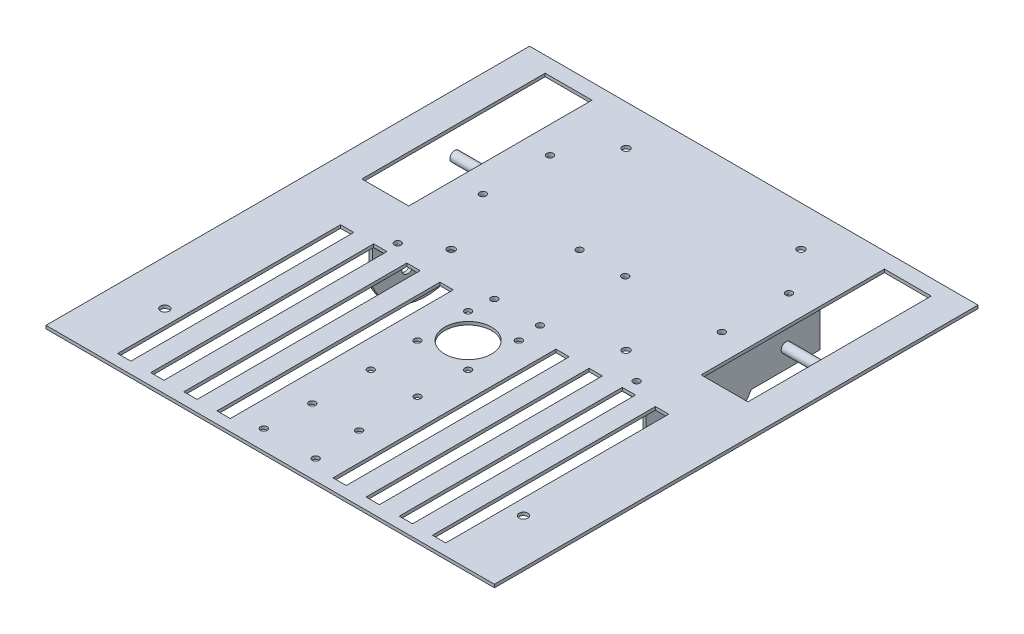
SolidWorks part; units mm, degrees
ref_plane "Front Plane" through (0, 0, 0) normal (0, 0, 1) x (1, 0, 0)
ref_plane "Top Plane" through (0, 0, 0) normal (0, 1, 0) x (1, 0, 0)
ref_plane "Right Plane" through (0, 0, 0) normal (1, 0, 0) x (0, 0, -1)
sketch "Sketch2" plane through (0, 0, 0) normal (0, 1, 0) x (1, 0, 0)
  line L7 (-172.2662, -88.2141) -> (57.7338, -88.2141)
  line L8 (17.7338, 151.7859) -> (41.7338, 151.7859)
  line L45 (17.7338, 151.7859) -> (17.7338, 57.7859)
  line L46 (17.7338, 57.7859) -> (41.7338, 57.7859)
  line L47 (41.7338, 151.7859) -> (41.7338, 57.7859)
  line L48 (-156.2662, 151.7859) -> (-132.2662, 151.7859)
  line L49 (-156.2662, 151.7859) -> (-156.2662, 57.7859)
  line L50 (-156.2662, 57.7859) -> (-132.2662, 57.7859)
  line L51 (-132.2662, 151.7859) -> (-132.2662, 57.7859)
  line L72 (57.7338, 159.7859) -> (-172.2662, 159.7859)
  line L74 (57.7338, -88.2141) -> (57.7338, 159.7859)
  line L79 (-172.2662, -88.2141) -> (-172.2662, 159.7859)
  dimension "D2" = 16
  dimension "D3" = 16
  dimension "D6" = 230
  dimension "D8" = 24
  dimension "D9" = 24
  dimension "D12" = 8
  dimension "D13" = 94
extrude "Boss-Extrude1" add sketch "Sketch2" along normal blind 1.6
ref_plane "Plane3" through (-57.2662, 0, 0) normal (1, 0, 0) x (0, 0, -1)
sketch "Sketch4" plane through (0, 0, 0) normal (0, -1, 0) x (1, 0, 0)
  line L0 (-128.2662, -122.8126) -> (-128.2662, -33.5103)
  line L1 (-128.2662, -122.8126) -> (-110.4256, -122.8126)
  line L2 (-128.2662, -33.5103) -> (-110.4287, -33.5103)
  line L5 (-64.765, -32.9867) -> (-64.765, -87.1773)
  line L6 (-64.765, -32.9867) -> (-73.1795, -32.9867)
  line L7 (-64.765, -87.1773) -> (-73.1795, -87.1773)
  line L9 (-110.4287, -33.5103) -> (-110.4287, -55.4044)
  line L10 (-110.4287, -55.4044) -> (-73.1795, -55.4044)
  line L11 (-73.1795, -55.4044) -> (-73.1795, -32.9867)
  line L12 (-73.1795, -87.1773) -> (-73.1795, -65.4044)
  line L13 (-73.1795, -65.4044) -> (-110.4256, -65.4044)
  line L14 (-110.4256, -65.4044) -> (-110.4256, -122.8126)
extrude "Boss-Extrude3" add sketch "Sketch4" along normal blind 1.6129 separate body
sketch "Sketch6" plane through (-128.2662, 113.8349, 0) normal (1, 0, 0) x (0, -1, 0)
  line L0 (115.4478, 33.5103) -> (113.8349, 33.5103)
  line L1 (113.8349, 33.5103) -> (113.8349, 122.8126)
  line L4 (132.89, 33.5103) -> (115.4478, 33.5103)
  line L7 (135.5889, 122.8126) -> (113.8349, 122.8126)
  line L8 (113.8349, 57.7859) -> (113.8349, 151.7859) construction
  line L10 (115.4478, 122.8126) -> (113.8349, 122.8126) construction
  line L11 (135.5889, 122.8126) -> (135.5889, 87.5048)
  circle A2 centre (133.4041, 73.86) radius 1.27
  circle A4 centre (133.4041, 51.6858) radius 3
  circle A5 centre (125.8349, 105.4126) radius 2.55
  circle A6 centre (123.1933, 51.6858) radius 1.27
  circle A8 centre (143.6149, 51.6858) radius 1.27
  arc A10 (135.5889, 87.5048) -> (132.89, 33.5103) centre (121.2431, 61.1572) cw
  line M25 (113.8349, 33.5103) -> (113.8349, 122.8126)
  line M26 (113.8349, 122.8126) -> (115.4478, 122.8126)
  line M27 (115.4478, 122.8126) -> (115.4478, 33.5103)
  line M28 (115.4478, 33.5103) -> (113.8349, 33.5103)
  dimension "D1" = 5.1
  dimension "D3" = 17.4
  dimension "D4" = 6
  dimension "D2" = 12
extrude "Boss-Extrude4" add sketch "Sketch6" along normal blind 1.6129 contours M28 M25 M26 M27 | L4 M27 | A6 A2 A4 A8 region at (-128.2662, -15.7003, -74.0989) region at (-128.2662, -0.8065, -78.1615)
sketch "Sketch7" plane through (0, -1.6129, 0) normal (0, -1, 0) x (1, 0, 0)
  line L0 (-172.2662, 88.2141) -> (57.7338, 88.2141) construction
  line L1 (-57.2662, -1.2799) -> (-57.2662, -25.2799)
  line L31 (-124.414, -31.9949) -> (-124.414, 82.3679)
  line L32 (-141.414, -31.9949) -> (-134.6033, -31.9949)
  line L33 (-141.414, -31.9949) -> (-141.414, 82.3679)
  line L34 (-141.414, 82.3679) -> (-134.6033, 82.3679)
  line L35 (-134.6033, -31.9949) -> (-134.6033, 82.3679)
  line L36 (-124.414, -31.9949) -> (-117.6033, -31.9949)
  line L37 (-124.414, 82.3679) -> (-117.6033, 82.3679)
  line L38 (-117.6033, -31.9949) -> (-117.6033, 82.3679)
  line L39 (-107.414, -31.9949) -> (-107.414, 82.3679)
  line L40 (-107.414, -31.9949) -> (-100.6033, -31.9949)
  line L41 (-107.414, 82.3679) -> (-100.6033, 82.3679)
  line L42 (-100.6033, -31.9949) -> (-100.6033, 82.3679)
  line L43 (-90.414, -31.9949) -> (-90.414, 82.3679)
  line L44 (-90.414, -31.9949) -> (-83.6033, -31.9949)
  line L45 (-90.414, 82.3679) -> (-83.6033, 82.3679)
  line L46 (-83.6033, -31.9949) -> (-83.6033, 82.3679)
  line L47 (-132.2662, -57.7859) -> (-132.2662, -151.7859) construction
  circle A0 centre (-118.541, -82.125) radius 1.7
  circle A1 centre (-118.541, -38.4299) radius 1.7
  circle A2 centre (-68.9723, -38.4299) radius 1.7
  circle A3 centre (-68.9723, -82.125) radius 1.7
  circle A4 centre (-118.541, -116.5476) radius 1.7
  circle A5 centre (-102.1184, -49.4299) radius 1.9
  circle A6 centre (-102.1184, -139.1299) radius 1.9
  circle A7 centre (-149.2312, 50.2851) radius 2.25
  circle A8 centre (-70.2662, -0.2799) radius 1.7
  circle A9 centre (-70.2662, -26.2799) radius 1.7
  arc A11 (-57.2662, -1.2799) -> (-57.2662, -25.2799) centre (-57.2662, -13.2799) ccw
  circle A12 centre (-70.5662, 78.2141) radius 1.7
  circle A13 centre (-69.2662, 24.6349) radius 1.7
  circle A14 centre (-69.2662, 54.6349) radius 1.7
  point P19 (-57.264, -94.2799)
  point P29 (-57.2662, 88.2141)
  point P37 (0, 0)
  point P50 (0, 0)
  dimension "D3" = 3.4
  dimension "D4" = 3.4
  dimension "D5" = 3.4
  dimension "D6" = 3.4
  dimension "D1" = 3.4
  dimension "D2" = 3.8
  dimension "D8" = 3.8
  dimension "D9" = 4.5
  dimension "D12" = 3.4
  dimension "D13" = 3.4
  dimension "D14" = 12
  dimension "D20" = 3.4
  dimension "D23" = 3.4
  dimension "D24" = 3.4
  dimension "D7" = 89.7
  dimension "D10" = 91.965
  dimension "D11" = 144.565
  dimension "D15" = 13
  dimension "D16" = 68
  dimension "D17" = 13
  dimension "D18" = 26
  dimension "D19" = 13
  dimension "D21" = 13.3
  dimension "D22" = 10
  dimension "D25" = 30
  dimension "D26" = 12
  dimension "D28" = 49.5687
  dimension "D29" = 13.7252
  dimension "D27" = 4
extrude "Cut-Extrude1" cut sketch "Sketch7" against normal blind 10
mirror "Mirror1" about plane through (-57.2662, 0, 0) normal (1, 0, 0) of bodies 157 158 103
mirror "Mirror2" about plane through (-57.2662, 0, 0) normal (1, 0, 0) of "Cut-Extrude1"
sketch "Sketch9" plane through (-156.2662, 0, 0) normal (1, 0, 0) x (0, 0, -1)
  circle A0 centre (105.4126, -12) radius 2.5
extrude "Boss-Extrude6" add sketch "Sketch9" along normal blind 189 separate body
equation "\"hardboard_width\"= 3.175"
equation "\"D1@Boss-Extrude1\"=\"hardboard_width\""
equation "\"steel_24g_thickness\"= 0.5"
equation "\"m3_clearance_hole\"= 3.4"
equation "\"D3@Sketch7\"=\"m3_clearance_hole\""
equation "\"D4@Sketch7\"=\"m3_clearance_hole\""
equation "\"D5@Sketch7\"=\"m3_clearance_hole\""
equation "\"D6@Sketch7\"=\"m3_clearance_hole\""
equation "\"steel_16g_thickness\"=1.6129"
equation "\"D1@Boss-Extrude3\"=\"steel_16g_thickness\""
equation "\"D1@Boss-Extrude4\"=\"steel_16g_thickness\""
equation "\"D1@Sketch7\"=\"m3_clearance_hole\""
equation "\"D12@Sketch7\"=\"m3_clearance_hole\""
equation "\"D20@Sketch7\"=\"m3_clearance_hole\""
equation "\"D23@Sketch7\"=\"m3_clearance_hole\""
equation "\"D24@Sketch7\"=\"m3_clearance_hole\""
